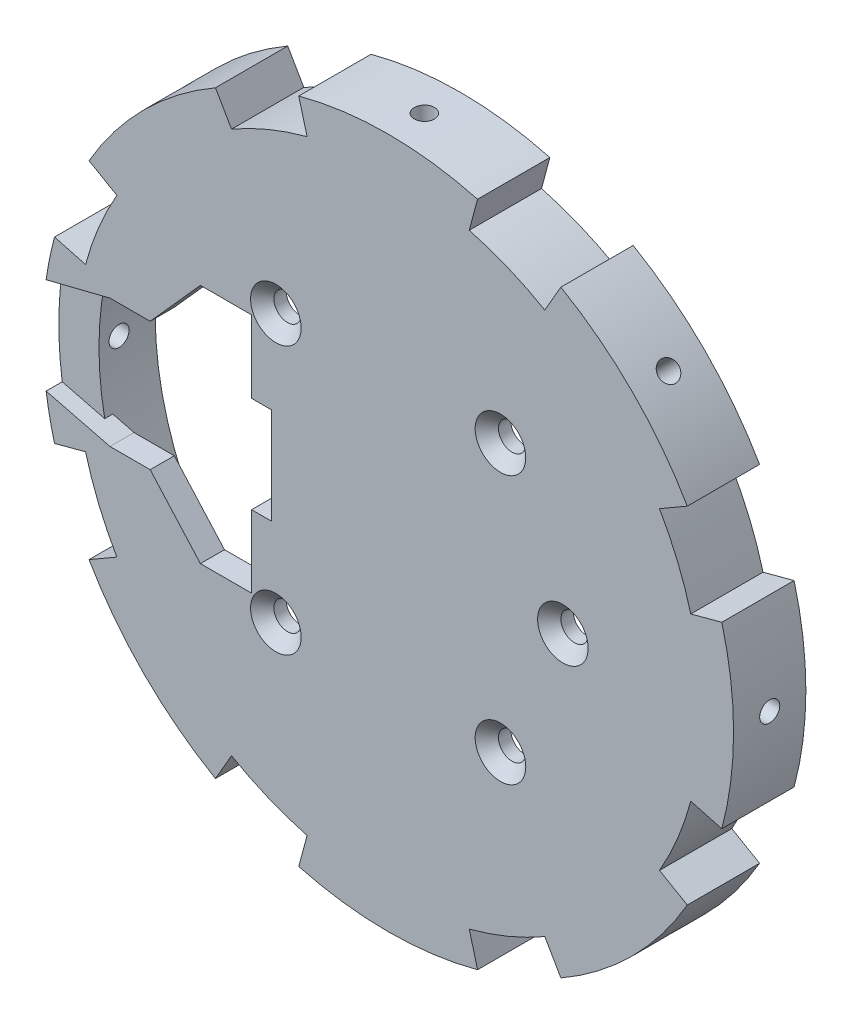
SolidWorks part; units mm, degrees
ref_plane "前视基准面" through (0, 0, 0) normal (0, 0, 1) x (1, 0, 0)
ref_plane "上视基准面" through (0, 0, 0) normal (0, 1, 0) x (1, 0, 0)
ref_plane "右视基准面" through (0, 0, 0) normal (1, 0, 0) x (0, 0, -1)
sketch "草图1" plane through (0, 0, 0) normal (0, 0, 1) x (1, 0, 0)
  line L16 (21.5, 37.2391) -> (19.5, 33.775)
  line L17 (11.1292, 41.5348) -> (10.0939, 37.6711)
  line L18 (-11.1292, 41.5348) -> (-10.0939, 37.6711)
  line L19 (37.2391, 21.5) -> (33.775, 19.5)
  line L20 (41.5348, 11.1292) -> (37.6711, 10.0939)
  line L21 (41.5348, -11.1292) -> (37.6711, -10.0939)
  line L22 (37.2391, -21.5) -> (33.775, -19.5)
  line L23 (21.5, -37.2391) -> (19.5, -33.775)
  line L24 (11.1292, -41.5348) -> (10.0939, -37.6711)
  line L25 (-11.1292, -41.5348) -> (-10.0939, -37.6711)
  line L26 (-21.5, -37.2391) -> (-19.5, -33.775)
  line L27 (-37.2391, -21.5) -> (-33.775, -19.5)
  line L28 (-41.5348, -11.1292) -> (-37.6711, -10.0939)
  line L29 (-41.5348, 11.1292) -> (-37.6711, 10.0939)
  line L30 (-37.2391, 21.5) -> (-33.775, 19.5)
  line L31 (-21.5, 37.2391) -> (-19.5, 33.775)
  circle A1 centre (0, 0) radius 38
  arc A6 (0, 43) -> (-11.1292, 41.5348) centre (0, 0) ccw
  arc A31 (0, 43) -> (11.1292, 41.5348) centre (0, 0) cw
  arc A32 (10.0939, 37.6711) -> (19.5, 33.775) centre (0, 0) cw
  arc A33 (30.4056, 30.4056) -> (21.5, 37.2391) centre (0, 0) ccw
  arc A34 (30.4056, 30.4056) -> (37.2391, 21.5) centre (0, 0) cw
  arc A35 (33.775, 19.5) -> (37.6711, 10.0939) centre (0, 0) cw
  arc A36 (43, 0) -> (41.5348, 11.1292) centre (0, 0) ccw
  arc A37 (43, 0) -> (41.5348, -11.1292) centre (0, 0) cw
  arc A38 (37.6711, -10.0939) -> (33.775, -19.5) centre (0, 0) cw
  arc A39 (30.4056, -30.4056) -> (37.2391, -21.5) centre (0, 0) ccw
  arc A40 (30.4056, -30.4056) -> (21.5, -37.2391) centre (0, 0) cw
  arc A41 (19.5, -33.775) -> (10.0939, -37.6711) centre (0, 0) cw
  arc A42 (0, -43) -> (11.1292, -41.5348) centre (0, 0) ccw
  arc A43 (0, -43) -> (-11.1292, -41.5348) centre (0, 0) cw
  arc A44 (-10.0939, -37.6711) -> (-19.5, -33.775) centre (0, 0) cw
  arc A45 (-30.4056, -30.4056) -> (-21.5, -37.2391) centre (0, 0) ccw
  arc A46 (-30.4056, -30.4056) -> (-37.2391, -21.5) centre (0, 0) cw
  arc A47 (-33.775, -19.5) -> (-37.6711, -10.0939) centre (0, 0) cw
  arc A48 (-43, 0) -> (-41.5348, -11.1292) centre (0, 0) ccw
  arc A49 (-43, 0) -> (-41.5348, 11.1292) centre (0, 0) cw
  arc A50 (-37.6711, 10.0939) -> (-33.775, 19.5) centre (0, 0) cw
  arc A51 (-30.4056, 30.4056) -> (-37.2391, 21.5) centre (0, 0) ccw
  arc A52 (-30.4056, 30.4056) -> (-21.5, 37.2391) centre (0, 0) cw
  arc A53 (-19.5, 33.775) -> (-10.0939, 37.6711) centre (0, 0) cw
  point P55 (0, 0)
  point P56 (0, 0)
  dimension "D1" = 8
extrude "凸台-拉伸1" add sketch "草图1" against normal blind 6
sketch "草图2" plane through (0, 0, 0) normal (0, 0, 1) x (1, 0, 0)
  line L16 (-11.1292, 41.5348) -> (-10.0939, 37.6711)
  line L17 (10.0939, 37.6711) -> (11.1292, 41.5348)
  line L18 (21.5, 37.2391) -> (19.5, 33.775)
  line L19 (33.775, 19.5) -> (37.2391, 21.5)
  line L20 (41.5348, 11.1292) -> (37.6711, 10.0939)
  line L21 (37.6711, -10.0939) -> (41.5348, -11.1292)
  line L22 (37.2391, -21.5) -> (33.775, -19.5)
  line L23 (19.5, -33.775) -> (21.5, -37.2391)
  line L24 (11.1292, -41.5348) -> (10.0939, -37.6711)
  line L25 (-10.0939, -37.6711) -> (-11.1292, -41.5348)
  line L26 (-21.5, -37.2391) -> (-19.5, -33.775)
  line L27 (-33.775, -19.5) -> (-37.2391, -21.5)
  line L28 (-41.5348, -11.1292) -> (-37.6711, -10.0939)
  line L29 (-37.6711, 10.0939) -> (-41.5348, 11.1292)
  line L30 (-37.2391, 21.5) -> (-33.775, 19.5)
  line L31 (-19.5, 33.775) -> (-21.5, 37.2391)
  arc A27 (0, 43) -> (11.1292, 41.5348) centre (0, 0) cw
  arc A28 (10.0939, 37.6711) -> (19.5, 33.775) centre (0, 0) cw
  arc A29 (0, 43) -> (-11.1292, 41.5348) centre (0, 0) ccw
  arc A30 (30.4056, 30.4056) -> (21.5, 37.2391) centre (0, 0) ccw
  arc A31 (30.4056, 30.4056) -> (37.2391, 21.5) centre (0, 0) cw
  arc A32 (33.775, 19.5) -> (37.6711, 10.0939) centre (0, 0) cw
  arc A33 (43, 0) -> (41.5348, 11.1292) centre (0, 0) ccw
  arc A34 (43, 0) -> (41.5348, -11.1292) centre (0, 0) cw
  arc A35 (37.6711, -10.0939) -> (33.775, -19.5) centre (0, 0) cw
  arc A36 (30.4056, -30.4056) -> (37.2391, -21.5) centre (0, 0) ccw
  arc A37 (30.4056, -30.4056) -> (21.5, -37.2391) centre (0, 0) cw
  arc A38 (19.5, -33.775) -> (10.0939, -37.6711) centre (0, 0) cw
  arc A39 (0, -43) -> (11.1292, -41.5348) centre (0, 0) ccw
  arc A40 (0, -43) -> (-11.1292, -41.5348) centre (0, 0) cw
  arc A41 (-10.0939, -37.6711) -> (-19.5, -33.775) centre (0, 0) cw
  arc A42 (-30.4056, -30.4056) -> (-21.5, -37.2391) centre (0, 0) ccw
  arc A43 (-30.4056, -30.4056) -> (-37.2391, -21.5) centre (0, 0) cw
  arc A44 (-33.775, -19.5) -> (-37.6711, -10.0939) centre (0, 0) cw
  arc A45 (-43, 0) -> (-41.5348, -11.1292) centre (0, 0) ccw
  arc A46 (-43, 0) -> (-41.5348, 11.1292) centre (0, 0) cw
  arc A47 (-37.6711, 10.0939) -> (-33.775, 19.5) centre (0, 0) cw
  arc A48 (-30.4056, 30.4056) -> (-37.2391, 21.5) centre (0, 0) ccw
  arc A49 (-30.4056, 30.4056) -> (-21.5, 37.2391) centre (0, 0) cw
  arc A50 (-19.5, 33.775) -> (-10.0939, 37.6711) centre (0, 0) cw
  point P43 (0, 0)
extrude "凸台-拉伸2" add sketch "草图2" along normal blind 3
hole_wizard "M3 锥坑平头的锥孔1" positions "3D草图2" profile "草图4" countersink size "M3" standard "BSI" end condition through all
sketch3d "3D草图2"
  point P25 (13.9806, -16.6615, 3)
  point P27 (21.75, 0, 3)
  point P40 (13.9806, 16.6615, 3)
  point P41 (-13.9806, -16.6615, 3)
  point P42 (-21.75, 0, 3)
  point P43 (-13.9806, 16.6615, 3)
sketch "草图4" plane through (13.9806, -16.6615, 3) normal (1, 0, 0) x (0, -1, 0)
  line L0 (0, 0) -> (0, 9)
  line L1 (0, 9) -> (1.7, 9)
  line L2 (1.7, 9) -> (1.7, 1.45)
  line L3 (1.7, 1.45) -> (3.15, 0)
  line L5 (3.15, 0) -> (0, 0)
  line L6 (-1.7, 1.45) -> (-3.15, 0) construction
  line L11 (0, -6.35) -> (0, 107.95) construction
  dimension "通孔孔直径" = 3.4
  dimension "通孔孔深度" = 9
  dimension "近端锥形沉头孔直径" = 6.3
  dimension "近端锥形沉头孔角度" = 90
hole_wizard "M3x0.5 螺纹孔1" positions "3D草图3" profile "草图5" tap size "M3x0.5" standard "BSI" end condition up to next
sketch3d "3D草图3"
  point P5 (0, -43, -1.5)
  point P13 (30.4056, -30.4056, -1.5)
  point P33 (30.4056, 30.4056, -1.5)
  point P43 (43, 0, -1.5)
  point P53 (-30.4056, 30.4056, -1.5)
  point P55 (-30.4056, -30.4056, -1.5)
  point P57 (43, 0, -1.5)
  point P72 (-43, 0, -1.5)
  point P77 (0, 43, -1.5)
sketch "草图5" plane through (0, -43, -1.5) normal (1, 0, 0) x (0, 0, -1)
  line L0 (0, 0) -> (0, 5)
  line L1 (0, 5) -> (1.25, 5)
  line L2 (1.25, 5) -> (1.25, 0)
  line L5 (1.25, 0) -> (0, 0)
  line L11 (0, -6.35) -> (0, 107.95) construction
  dimension "通孔螺纹孔钻头直径" = 2.5
  dimension "通孔螺纹孔钻头深度" = 5
cosmetic thread "孔螺蚊线1" parameters "D2"=3
cosmetic thread "孔螺蚊线2" parameters "D2"=3
cosmetic thread "孔螺蚊线3" parameters "D2"=3
cosmetic thread "孔螺蚊线4" parameters "D2"=3
cosmetic thread "孔螺蚊线5" parameters "D2"=3
cosmetic thread "孔螺蚊线6" parameters "D2"=3
sketch "草图6" plane through (0, 0, 0) normal (0, 0, 1) x (1, 0, 0)
  line L3 (-14.5, -6) -> (-14.5, 6)
  line L4 (-14.5, 6) -> (-17, 6)
  line L9 (-17, 15) -> (-23.3746, 15)
  line L10 (-23.3746, 15) -> (-29.6246, 8)
  line L12 (-29.6246, 8) -> (-34.6246, 8)
  line L13 (-14.5, -6) -> (-17, -6)
  line L16 (-17, -15) -> (-23.3746, -15)
  line L17 (-23.3746, -15) -> (-29.6246, -8)
  line L20 (-34.6246, -8) -> (-29.6246, -8)
  line L21 (-17, -15) -> (-17, -6)
  line L22 (-42.5793, 6) -> (-34.6246, 8)
  line L23 (-42.5793, -6) -> (-34.6246, -8)
  line L24 (-17, 6) -> (-17, 15)
  arc A2 (-41.5348, 11.1292) -> (-41.5348, -11.1292) centre (0, 0) ccw construction
  arc A3 (-42.5793, 6) -> (-42.5793, -6) centre (0, 0) ccw
extrude "切除-拉伸1" cut sketch "草图6" along normal blind 3
sketch "草图9" plane through (0, 0, 0) normal (0, 0, 1) x (1, 0, 0)
  line L0 (-34.6246, 8) -> (-42.5793, 6) construction
  line L1 (-37.2862, 7.3308) -> (-42.5793, 6) construction
  line L2 (-42.5793, 6) -> (-37.2862, 7.3308)
  line L3 (-42.5793, -6) -> (-37.2862, -7.3308)
  arc A0 (-37.2862, -7.3308) -> (-37.2862, 7.3308) centre (0, 0) cw
  arc A1 (-42.5793, -6) -> (-42.5793, 6) centre (0, 0) cw
extrude "凸台-拉伸3" add sketch "草图9" along normal blind 1
